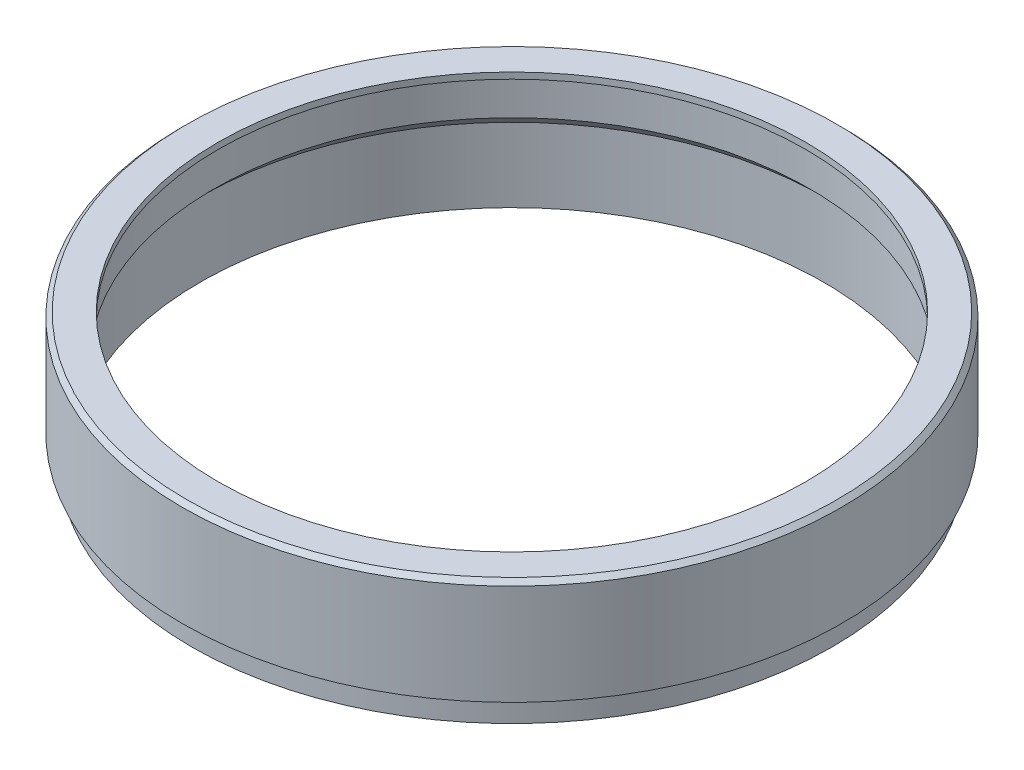
SolidWorks part; units mm, degrees
ref_plane "Front Plane" through (0, 0, 0) normal (0, 0, 1) x (1, 0, 0)
ref_plane "Top Plane" through (0, 0, 0) normal (0, 1, 0) x (1, 0, 0)
ref_plane "Right Plane" through (0, 0, 0) normal (1, 0, 0) x (0, 0, -1)
ref_axis "Axis1" through (0, 0, 0) along (0, 1, 0)
sketch "Sketch1" plane through (0, 0, 0) normal (0, 0, 1) x (1, 0, 0)
  line L0 (0, 0) -> (0, -50000) construction
  line L1 (-35, 3.2) -> (-35, 11.5)
  line L2 (-35, 11.5) -> (-33.5, 13)
  line L3 (-33.5, 13) -> (-33.5, 17.1)
  line L4 (-33.5, 17.1) -> (-33, 17.1)
  line L5 (-33, 17.1) -> (-33, 17.8)
  line L6 (-33, 17.8) -> (-36.5, 17.8)
  line L7 (-36.5, 17.8) -> (-37, 17.3)
  line L8 (-37, 17.3) -> (-37, 6)
  line L9 (-37, 6) -> (-35.95, 6)
  line L10 (-35.95, 6) -> (-35.95, 3.2)
  line L11 (-35.95, 3.2) -> (-35, 3.2)
  line L12 (-35, -9.2) -> (-35, 3) construction
  line L13 (-37, 6) -> (-37, -13.9) construction
  line L15 (36, 6) -> (-36, 6) construction
  line L18 (-35, 3) -> (-36, 3) construction
  line L20 (33.5, 17.1) -> (-33.5, 17.1) construction
  dimension "D1" = 0.2
  dimension "D2" = 67
  dimension "D3" = 0.5
  dimension "D4" = 0.7
  dimension "D5" = 135
  dimension "D6" = 0.5
  dimension "D7" = 135
  dimension "D8" = 4.1
  dimension "D9" = 71.9
revolve "Revolve1" add sketch "Sketch1" angle 360 about L0
